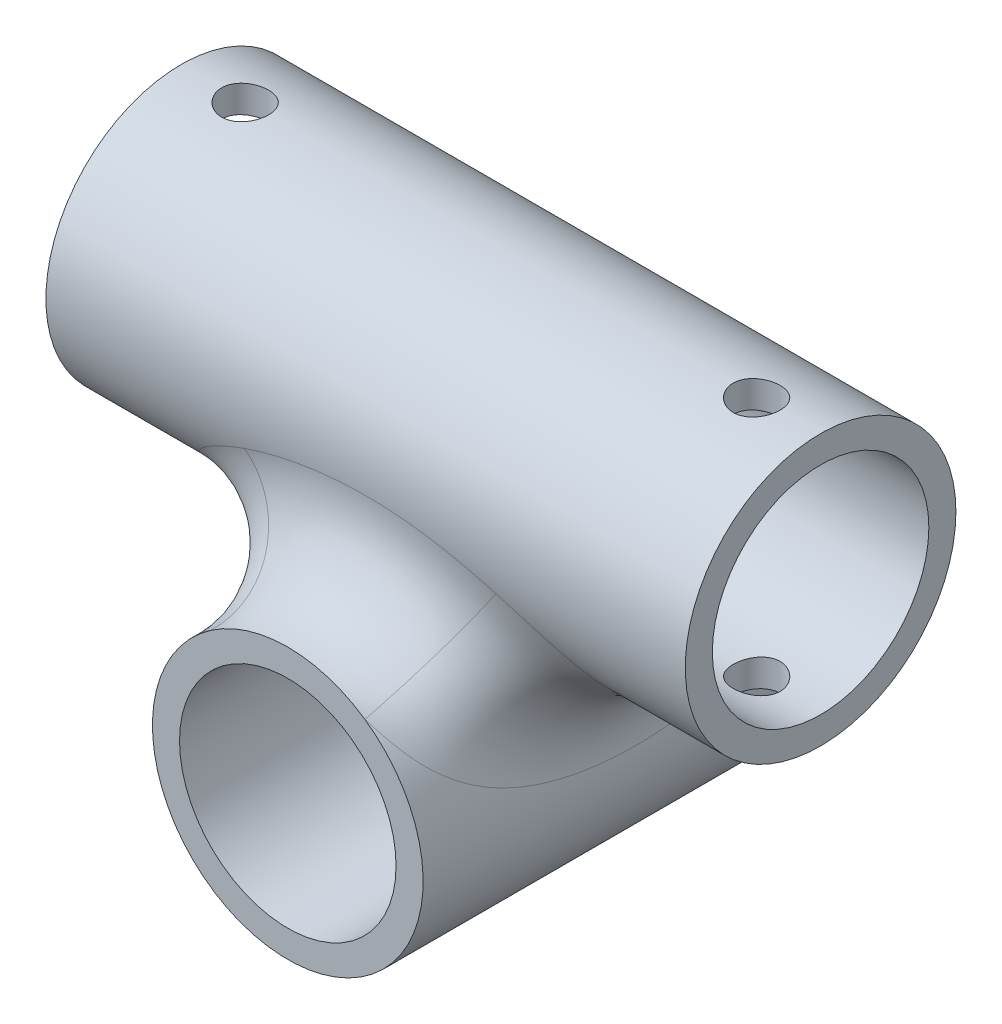
SolidWorks part; units mm, degrees
material "1060 Alloy"
ref_plane "Front Plane" through (0, 0, 0) normal (0, 0, 1) x (1, 0, 0)
ref_plane "Top Plane" through (0, 0, 0) normal (0, 1, 0) x (1, 0, 0)
ref_plane "Right Plane" through (0, 0, 0) normal (1, 0, 0) x (0, 0, -1)
sketch "Sketch1" plane through (0, 0, 0) normal (0, 0, 1) x (1, 0, 0)
  circle A0 centre (0, 0) radius 12.7
  circle A1 centre (0, 0) radius 15.875
  dimension "D1" = 25.4
  dimension "D2" = 31.75
extrude "Boss-Extrude1" add sketch "Sketch1" along normal mid plane 50
sketch "Sketch2" plane through (0, 0, 0) normal (1, 0, 0) x (0, 0, -1)
  circle A0 centre (0, 27.94) radius 12.7
  circle A1 centre (0, 27.94) radius 15.875
  dimension "D2" = 31.75
  dimension "D1" = 25.4
  dimension "D3" = 27.94
extrude "Boss-Extrude2" add sketch "Sketch2" along normal mid plane 75
fillet "Fillet1" radius 10 1 edges at (-2.6018, 15.6603, -10.0611)
ref_plane "Plane1" through (0, 43.815, 0) normal (0, 1, 0) x (1, 0, 0)
sketch "Sketch3" plane through (0, 43.815, 0) normal (0, 1, 0) x (1, 0, 0)
  line L0 (-30, 0) -> (30, 0) construction
  dimension "D1" = 60
hole_wizard "M5 Clearance Hole1" positions "Sketch4" profile "Sketch5" hole size "M5" standard "AS" end condition through all
sketch "Sketch4" plane through (0, 43.815, 0) normal (0, 1, 0) x (1, 0, 0)
  point P0 (-30, 0)
  point P3 (30, 0)
sketch "Sketch5" plane through (-30, 43.815, 0) normal (1, 0, 0) x (0, 0, 1)
  line L0 (0, 0) -> (0, 59.69)
  line L1 (0, 59.69) -> (2.75, 59.69)
  line L2 (2.75, 59.69) -> (2.75, 0)
  line L5 (2.75, 0) -> (0, 0)
  line L11 (0, -6.35) -> (0, 107.95) construction
  dimension "Thru Hole Dia." = 5.5
  dimension "Thru Hole Depth" = 59.69
equation "\"keelOutDiameter\"= 1in"
equation "\"keelInDiameter\"= \"keelOutDiameter\" - 0.125in"
equation "\"frontBoltClearance\"= 7.25mm"
equation "\"betweenBoltsDistance\"= 20mm"
equation "\"wingLength\"= 1.4m"
equation "\"frontTubeLength\"= \"wingLength\" / sin ( 34.95deg )"
equation "\"plateThickness\"= 5mm"
equation "\"crossBarOutDiameter\"= 1in"
equation "\"crossBarInDiameter\"= \"crossBarOutDiameter\" - 0.125in"
equation "\"frontToCrossBar\"= 466mm"
equation "\"D1@Sketch1\"=\"keelOutDiameter\""
equation "\"D2@Sketch1\"=\"keelOutDiameter\"+0.25in"
equation "\"D1@Sketch2\"=\"crossBarOutDiameter\""
equation "\"D2@Sketch2\"=\"crossBarOutDiameter\"+0.25in"
equation "\"D3@Sketch2\"=(\"crossBarOutDiameter\"+\"keelOutDiameter\")/4+0.6in"
equation "\"D1@Fillet1\"=\"crossBarOutDiameter\"/2.54"
